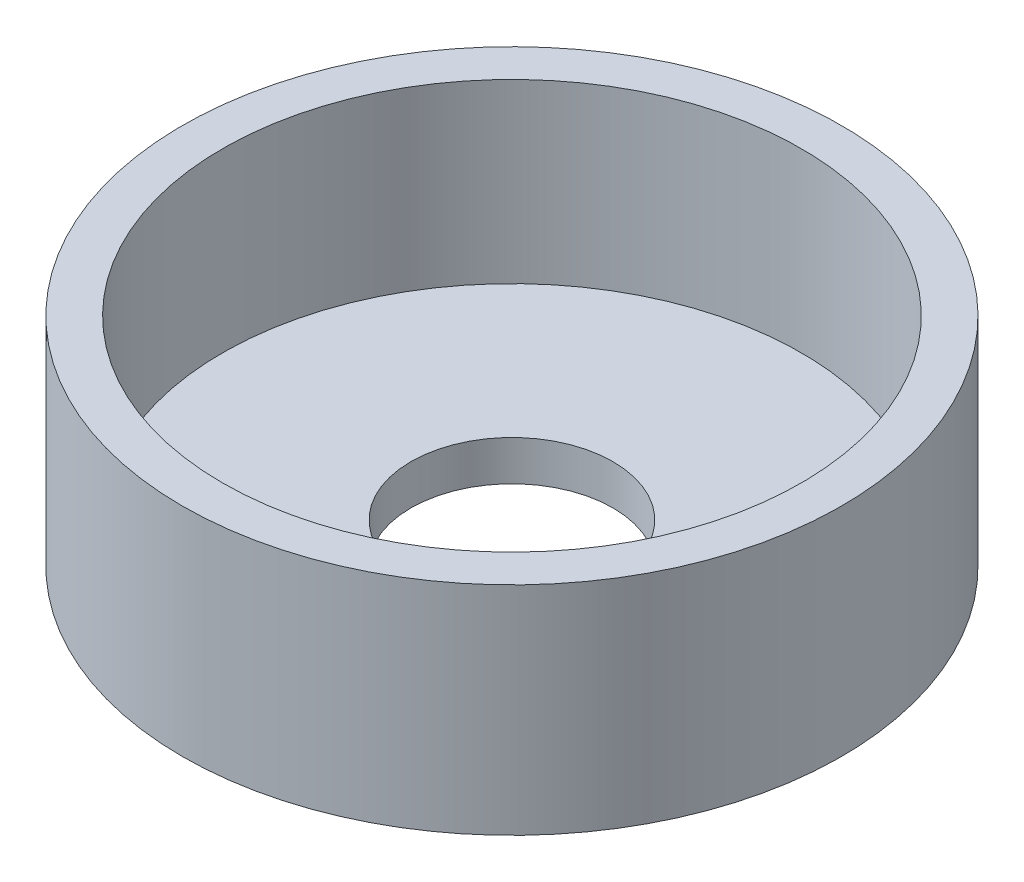
SolidWorks part; units mm, degrees
ref_plane "Front Plane" through (0, 0, 0) normal (0, 0, 1) x (1, 0, 0)
ref_plane "Top Plane" through (0, 0, 0) normal (0, 1, 0) x (1, 0, 0)
ref_plane "Right Plane" through (0, 0, 0) normal (1, 0, 0) x (0, 0, -1)
sketch "Sketch2" plane through (0, 0, 0) normal (0, 1, 0) x (1, 0, 0)
  circle A0 centre (0, 0) radius 11.4583
  dimension "D1" = 22.9167
extrude "Boss-Extrude1" add sketch "Sketch2" along normal blind 1.5875
sketch "Sketch5" plane through (0, 1.5875, 0) normal (0, 1, 0) x (1, 0, 0)
  circle A0 centre (0, 0) radius 13.0458
  circle A1 centre (0, 0) radius 11.4583
  dimension "D1" = 1.5875
  dimension "D2" = 22.9167
extrude "Boss-Extrude4" add sketch "Sketch5" against normal blind 1.5875 contours A0
extrude "Boss-Extrude5" add sketch "Sketch5<4>" along normal blind 7 contours A0 | A1
sketch "Sketch5<4>" plane through (0, 1.5875, 0) normal (0, 1, 0) x (1, 0, 0) same geometry as "Sketch5"
sketch "Sketch6" plane through (0, 1.5875, 0) normal (0, 1, 0) x (1, 0, 0)
  circle A0 centre (0, 0) radius 4.0005
  dimension "D1" = 8.001
extrude "Cut-Extrude1" cut sketch "Sketch6" against normal through all
